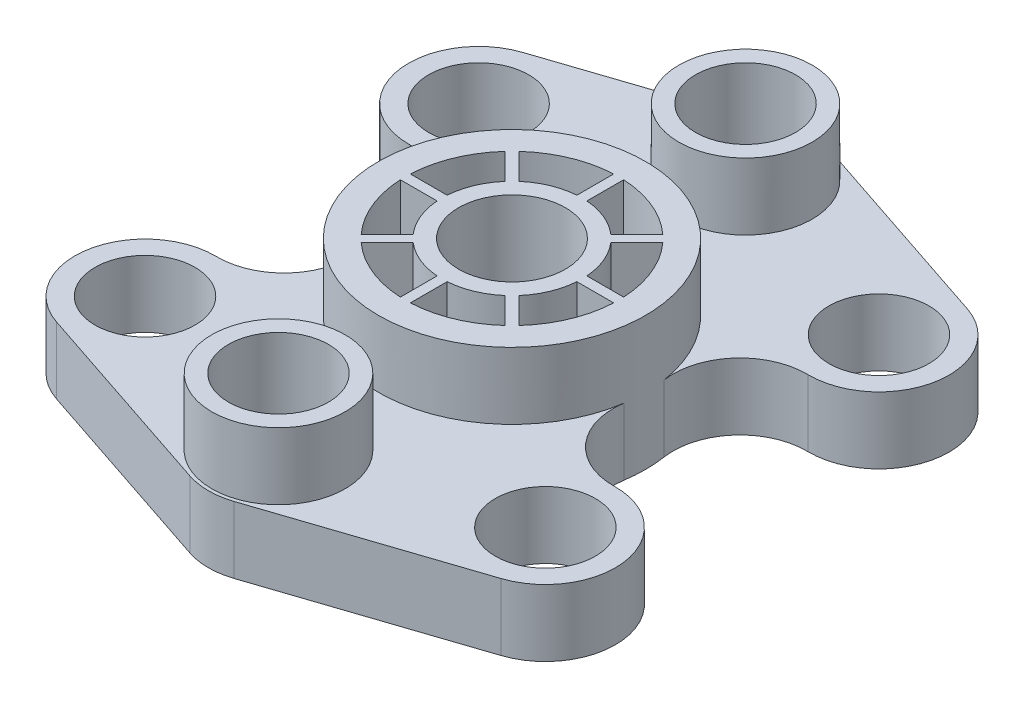
SolidWorks part; units mm, degrees
ref_plane "Front Plane" through (0, 0, 0) normal (0, 0, 1) x (1, 0, 0)
ref_plane "Top Plane" through (0, 0, 0) normal (0, 1, 0) x (1, 0, 0)
ref_plane "Right Plane" through (0, 0, 0) normal (1, 0, 0) x (0, 0, -1)
sketch "Sketch1" plane through (0, 0, 0) normal (0, 1, 0) x (1, 0, 0)
  line L0 (0, 0) -> (0, 173.0095) construction
  line L1 (0, 0) -> (99.7131, 0) construction
  line L2 (-66.6408, 69.9223) -> (-6.6408, 89.9223)
  line L3 (6.6408, 89.9223) -> (66.6408, 69.9223)
  line L4 (6.6408, -89.9223) -> (66.6408, -69.9223)
  line L5 (-66.6408, -69.9223) -> (-6.6408, -89.9223)
  arc A0 (-39.5469, 6.0038) -> (-39.5469, -6.0038) centre (0, 0) ccw
  arc A2 (6.6408, 89.9223) -> (-6.6408, 89.9223) centre (0, 70) ccw
  arc A3 (-66.6408, 69.9223) -> (-59.6519, 29.0029) centre (-60, 50) ccw
  arc A4 (59.6519, 29.0029) -> (66.6408, 69.9223) centre (60, 50) ccw
  arc A5 (59.6519, 29.0029) -> (39.5469, 6.0038) centre (59.3203, 9.0056) ccw
  arc A6 (-39.5469, 6.0038) -> (-59.6519, 29.0029) centre (-59.3203, 9.0056) ccw
  arc A7 (-39.5469, -6.0038) -> (-59.6519, -29.0029) centre (-59.3203, -9.0056) cw
  arc A8 (-66.6408, -69.9223) -> (-59.6519, -29.0029) centre (-60, -50) cw
  arc A9 (59.6519, -29.0029) -> (66.6408, -69.9223) centre (60, -50) cw
  arc A10 (59.6519, -29.0029) -> (39.5469, -6.0038) centre (59.3203, -9.0056) cw
  arc A11 (6.6408, -89.9223) -> (-6.6408, -89.9223) centre (0, -70) cw
  arc A12 (39.5469, -6.0038) -> (39.5469, 6.0038) centre (0, 0) ccw
  dimension "D1" = 80
  dimension "D3" = 42
  dimension "D8" = 40
  dimension "D4" = 50
  dimension "D5" = 60
  dimension "D6" = 60
  dimension "D7" = 20
extrude "Boss-Extrude2" add sketch "Sketch1" along normal blind 20
sketch "Sketch2" plane through (0, 20, 0) normal (0, 1, 0) x (1, 0, 0)
  circle A0 centre (0, 0) radius 40
  circle A2 centre (0, 70) radius 20
  circle A3 centre (60, 50) radius 15
  circle A4 centre (-60, 50) radius 15
  circle A5 centre (0, -70) radius 20
  circle A6 centre (60, -50) radius 15
  circle A7 centre (-60, -50) radius 15
  dimension "D1" = 80
  dimension "D2" = 30
  dimension "D3" = 40
extrude "Boss-Extrude3" add sketch "Sketch2" along normal blind 20 contours A5 | A2 | A0
extrude "Cut-Extrude1" cut sketch "Sketch2<5>" against normal blind 20 contours A4 | A3 | A6 | A7
sketch "Sketch2<5>" plane through (0, 20, 0) normal (0, 1, 0) x (1, 0, 0) same geometry as "Sketch2"
sketch "Sketch3" plane through (0, 40, 0) normal (0, 1, 0) x (1, 0, 0)
  line L0 (0, 0) -> (0, 118.7375) construction
  line L1 (0, 0) -> (150.5653, 0) construction
  line L2 (-1.5, 31.9648) -> (-1.5, 20.9464)
  line L3 (1.5, 31.9648) -> (1.5, 20.9464)
  line L4 (23.6632, 21.5419) -> (15.872, 13.7507)
  line L5 (21.5419, 23.6632) -> (13.7507, 15.872)
  line L6 (31.9648, -1.5) -> (20.9464, -1.5)
  line L7 (31.9648, 1.5) -> (20.9464, 1.5)
  line L8 (21.5419, -23.6632) -> (13.7507, -15.872)
  line L9 (23.6632, -21.5419) -> (15.872, -13.7507)
  line L10 (-1.5, -31.9648) -> (-1.5, -20.9464)
  line L11 (1.5, -31.9648) -> (1.5, -20.9464)
  line L12 (-23.6632, -21.5419) -> (-15.872, -13.7507)
  line L13 (-21.5419, -23.6632) -> (-13.7507, -15.872)
  line L14 (-31.9648, 1.5) -> (-20.9464, 1.5)
  line L15 (-31.9648, -1.5) -> (-20.9464, -1.5)
  line L16 (-21.5419, 23.6632) -> (-13.7507, 15.872)
  line L17 (-23.6632, 21.5419) -> (-15.872, 13.7507)
  arc A0 (-1.5, 31.9648) -> (-21.5419, 23.6632) centre (0, 0) ccw
  arc A1 (-1.5, 20.9464) -> (-13.7507, 15.872) centre (0, 0) ccw
  circle A2 centre (0, 0) radius 16
  arc A3 (13.7507, 15.872) -> (1.5, 20.9464) centre (0, 0) ccw
  arc A4 (21.5419, 23.6632) -> (1.5, 31.9648) centre (0, 0) ccw
  arc A5 (20.9464, 1.5) -> (15.872, 13.7507) centre (0, 0) ccw
  arc A6 (31.9648, 1.5) -> (23.6632, 21.5419) centre (0, 0) ccw
  arc A7 (-15.872, 13.7507) -> (-20.9464, 1.5) centre (0, 0) ccw
  arc A8 (-23.6632, 21.5419) -> (-31.9648, 1.5) centre (0, 0) ccw
  arc A9 (-31.9648, -1.5) -> (-23.6632, -21.5419) centre (0, 0) ccw
  arc A10 (-20.9464, -1.5) -> (-15.872, -13.7507) centre (0, 0) ccw
  arc A11 (-13.7507, -15.872) -> (-1.5, -20.9464) centre (0, 0) ccw
  arc A12 (-21.5419, -23.6632) -> (-1.5, -31.9648) centre (0, 0) ccw
  arc A13 (1.5, -31.9648) -> (21.5419, -23.6632) centre (0, 0) ccw
  arc A14 (1.5, -20.9464) -> (13.7507, -15.872) centre (0, 0) ccw
  arc A15 (15.872, -13.7507) -> (20.9464, -1.5) centre (0, 0) ccw
  arc A16 (23.6632, -21.5419) -> (31.9648, -1.5) centre (0, 0) ccw
  point P11 (28.6083, -2.3468)
  point P12 (0, 0)
  point P42 (0, 0)
  dimension "D1" = 64
  dimension "D2" = 42
  dimension "D3" = 32
  dimension "D4" = 3
  dimension "D5" = 8
extrude "Cut-Extrude2" cut sketch "Sketch3" against normal through all
sketch "Sketch4" plane through (0, 40, 0) normal (0, 1, 0) x (1, 0, 0)
  circle A0 centre (0, 70) radius 15
  circle A1 centre (0, -70) radius 15
  dimension "D1" = 30
extrude "Cut-Extrude3" cut sketch "Sketch4" against normal through all
